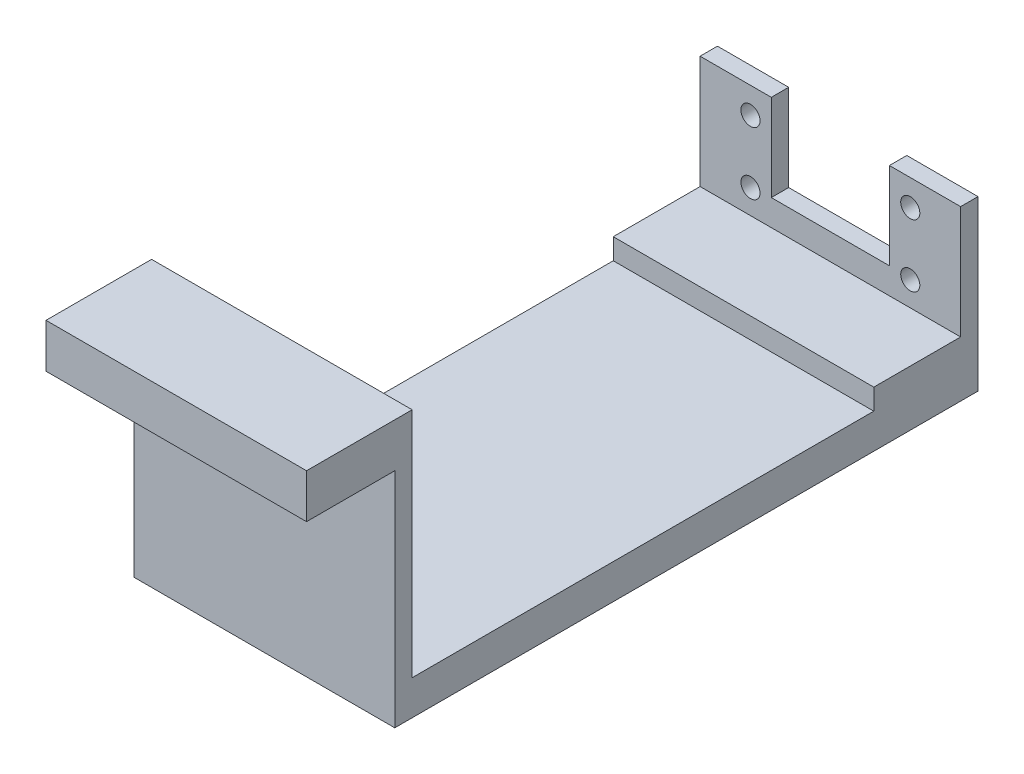
SolidWorks part; units mm, degrees
material "ABS"
ref_plane "Front Plane" through (0, 0, 0) normal (0, 0, 1) x (1, 0, 0)
ref_plane "Top Plane" through (0, 0, 0) normal (0, 1, 0) x (1, 0, 0)
ref_plane "Right Plane" through (0, 0, 0) normal (1, 0, 0) x (0, 0, -1)
sketch "Sketch1" plane through (0, 0, 0) normal (0, 0, 1) x (1, 0, 0)
  line L0 (20.5, 32.5) -> (20.5, 7.5)
  line L1 (0, 0) -> (75, 0)
  line L2 (0, 0) -> (0, 32.5)
  line L3 (0, 32.5) -> (75, 32.5)
  line L4 (75, 0) -> (75, 32.5)
  line L5 (20.5, 7.5) -> (54.5, 7.5)
  line L6 (54.5, 7.5) -> (54.5, 32.5)
  line L7 (37.5, 32.5) -> (37.5, 0) construction
  circle A0 centre (14.5, 25) radius 2.75
  circle A1 centre (14.5, 7) radius 2.75
  circle A2 centre (60.5, 7) radius 2.75
  circle A3 centre (60.5, 25) radius 2.75
  dimension "D6" = 5.5
  dimension "D7" = 46
  dimension "D8" = 34
  dimension "D1" = 32.5
  dimension "D2" = 75
  dimension "D3" = 17
  dimension "D4" = 18
  dimension "D5" = 25
  dimension "D9" = 25
  dimension "D10" = 14.5
  dimension "D11" = 6
extrude "Boss-Extrude1" add sketch "Sketch1" along normal blind 5 contours L7 L5 L0 L3 L2 L1 A1 A0 | L5 L7 L1 L4 L3 L6 A3 A2 region at (13.183, 14.1302, 0) region at (61.817, 14.1302, 0)
sketch "Sketch2" plane through (0, 0, 5) normal (0, 0, 1) x (1, 0, 0)
  line L0 (75, 0) -> (75, 32.5) construction
  line L1 (0, 0) -> (75, 0)
  line L2 (0, 0) -> (0, -6)
  line L3 (0, -6) -> (75, -6)
  line L4 (75, 0) -> (75, -6)
  dimension "D1" = 6
extrude "Boss-Extrude2" add sketch "Sketch2" along normal blind 25 and the other way blind 5
sketch "Sketch3" plane through (0, 0, 0) normal (0, 0, -1) x (-1, 0, 0)
  line L0 (0, -6) -> (0, 32.5) construction
  line L1 (-75, -6) -> (0, -6)
  line L2 (-75, -6) -> (-75, -16)
  line L3 (-75, -16) -> (0, -16)
  line L4 (0, -6) -> (0, -16)
  dimension "D1" = 10
extrude "Boss-Extrude3" add sketch "Sketch3" against normal blind 167.8942
sketch "Sketch4" plane through (0, -6, 0) normal (0, 1, 0) x (1, 0, 0)
  line L0 (75, -167.8942) -> (75, -30) construction
  line L1 (0, -167.8942) -> (75, -167.8942)
  line L2 (0, -167.8942) -> (0, -162.8942)
  line L3 (0, -162.8942) -> (75, -162.8942)
  line L4 (75, -167.8942) -> (75, -162.8942)
  dimension "D1" = 5
extrude "Boss-Extrude4" add sketch "Sketch4" along normal blind 66.8
sketch "Sketch5" plane through (0, 0, 167.8942) normal (0, 0, 1) x (1, 0, 0)
  line L0 (0, -16) -> (0, 60.8) construction
  line L1 (0, 48.1) -> (75, 48.1)
  line L2 (0, 48.1) -> (0, 60.8)
  line L3 (0, 60.8) -> (75, 60.8)
  line L4 (75, 48.1) -> (75, 60.8)
  line L5 (75, 60.8) -> (75, -16) construction
  line L6 (0, 60.8) -> (75, 60.8) construction
  dimension "D2" = 12.7
extrude "Boss-Extrude5" add sketch "Sketch5" along normal blind 25.4
